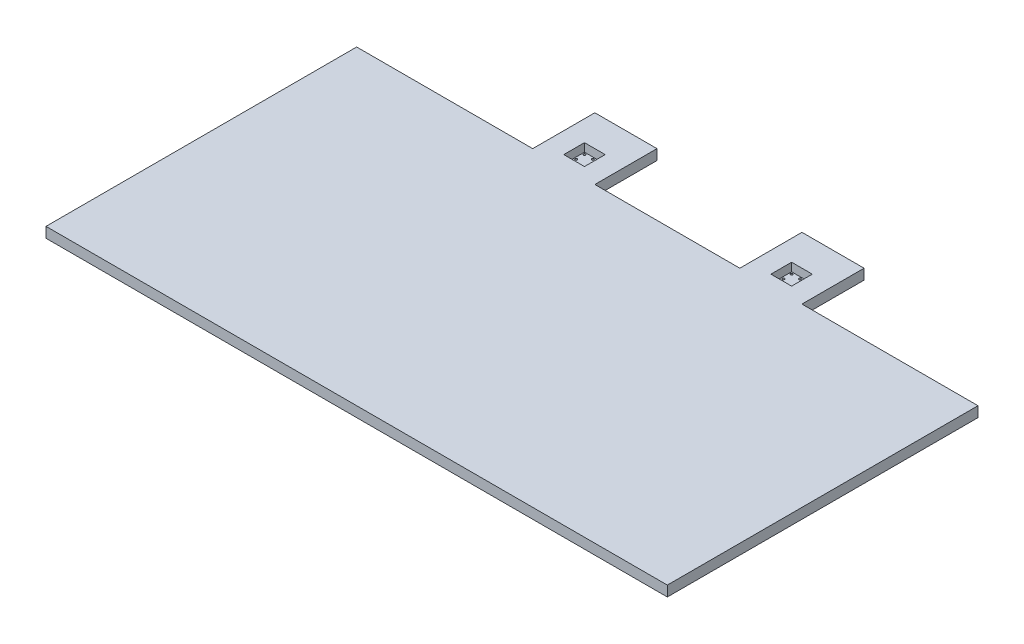
SolidWorks part; units mm, degrees
ref_plane "前基準面" through (0, 0, 0) normal (0, 0, 1) x (1, 0, 0)
ref_plane "上基準面" through (0, 0, 0) normal (0, 1, 0) x (1, 0, 0)
ref_plane "右基準面" through (0, 0, 0) normal (1, 0, 0) x (0, 0, -1)
sketch "草圖1" plane through (0, 0, 0) normal (0, 1, 0) x (1, 0, 0)
  line L0 (-100, -850) -> (-100, 49150) construction
  line L1 (-300, -150) -> (300, -150)
  line L2 (-300, -150) -> (-300, 150)
  line L3 (-300, 150) -> (-130, 150)
  line L4 (300, -150) -> (300, 150)
  line L7 (100, -850) -> (100, 49150) construction
  line L8 (-130, 150) -> (-130, 210)
  line L9 (-130, 210) -> (-70, 210)
  line L10 (-70, 210) -> (-70, 150)
  line L11 (70, 150) -> (70, 210)
  line L12 (70, 210) -> (130, 210)
  line L13 (130, 210) -> (130, 150)
  line L14 (-70, 150) -> (70, 150)
  line L15 (130, 150) -> (300, 150)
  point P0 (0, 0)
  point P16 (-100, 210)
  point P19 (100, 210)
  dimension "D1" = 600
  dimension "D2" = 300
  dimension "D3" = 200
  dimension "D4" = 200
  dimension "D5" = 60
  dimension "D6" = 60
  dimension "D7" = 60
extrude "填料-伸長1" add sketch "草圖1" along normal blind 10
sketch "草圖2" plane through (0, 10, 0) normal (0, 1, 0) x (1, 0, 0)
  line L0 (-1070, 170) -> (48930, 170) construction
  line L2 (-130, 150) -> (-300, 150) construction
  line L3 (0, -1000) -> (0, 49000) construction
  line L4 (-100, -790) -> (-100, 49210) construction
  line L5 (-70, 210) -> (-130, 210) construction
  line L6 (100, -790) -> (100, 49210) construction
  line L7 (130, 210) -> (70, 210) construction
  line L8 (110, 180) -> (90, 160) construction
  line L9 (-110, 160) -> (-90, 160)
  line L10 (-110, 160) -> (-110, 180)
  line L11 (-110, 180) -> (-90, 180)
  line L12 (-90, 160) -> (-90, 180)
  line L13 (-110, 160) -> (-90, 180) construction
  line L14 (-110, 180) -> (-90, 160) construction
  line L15 (110, 160) -> (90, 180) construction
  line L16 (90, 160) -> (90, 180)
  line L17 (110, 180) -> (90, 180)
  line L18 (110, 160) -> (110, 180)
  line L19 (110, 160) -> (90, 160)
  circle A0 centre (-108, 178) radius 1.05
  circle A1 centre (-92, 178) radius 1.05
  circle A2 centre (-92, 162) radius 1.05
  circle A3 centre (-108, 162) radius 1.05
  circle A4 centre (108, 162) radius 1.05
  circle A5 centre (92, 162) radius 1.05
  circle A6 centre (92, 178) radius 1.05
  circle A7 centre (108, 178) radius 1.05
  circle A8 centre (-100, 178) radius 1.05
  circle A9 centre (-100, 162) radius 1.05
  circle A10 centre (-108, 170) radius 1.05
  circle A11 centre (-92, 170) radius 1.05
  circle A12 centre (108, 170) radius 1.05
  circle A13 centre (100, 162) radius 1.05
  circle A14 centre (92, 170) radius 1.05
  circle A15 centre (100, 178) radius 1.05
  point P12 (-100, 210)
  point P17 (100, 210)
  point P25 (-100, 170)
  point P30 (-90, 170)
  point P43 (100, 170)
  point P46 (0, 0)
  point P51 (0, 0)
  dimension "D2" = 2.1
  dimension "D1" = 20
  dimension "D3" = 8
  dimension "D4" = 8
  dimension "D5" = 20
extrude "除料-伸長1" cut sketch "草圖2" against normal blind 8 contours L9 L12 L11 L10 A1 A0 A2 A3 | L19 L18 L17 L16 A5 A4 A6 A7 region at (-100, 10, -170) region at (100, 10, -170)
extrude "除料-伸長3" cut sketch "草圖2<4>" against normal through all contours A11 | A8 | A10 | A9 | A12 | A15 | A14 | A13 | A0 | A1 | A2 | A3 | A6 | A7 | A4 | A5 region at (-100, 10, -178) region at (-100, 10, -162) region at (-108, 10, -170) region at (-92, 10, -170) region at (108, 10, -170) region at (100, 10, -162) region at (92, 10, -170) region at (100, 10, -178)
sketch "草圖2<4>" plane through (0, 10, 0) normal (0, 1, 0) x (1, 0, 0) same geometry as "草圖2"
